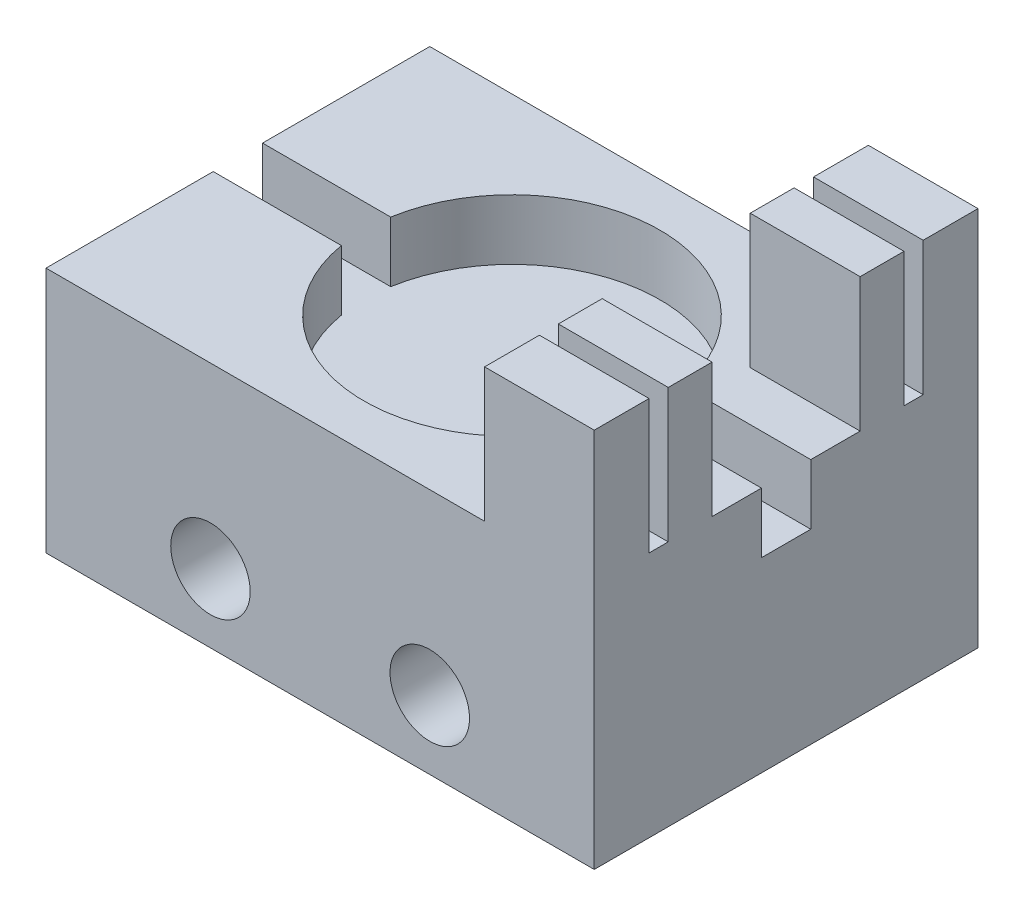
SolidWorks part; units mm, degrees
ref_plane "Front Plane" through (0, 0, 0) normal (0, 0, 1) x (1, 0, 0)
ref_plane "Top Plane" through (0, 0, 0) normal (0, 1, 0) x (1, 0, 0)
ref_plane "Right Plane" through (0, 0, 0) normal (1, 0, 0) x (0, 0, -1)
sketch "Sketch1" plane through (0, 0, 0) normal (0, 0, 1) x (1, 0, 0)
  line L1 (-25, -11.25) -> (25, -11.25)
  line L2 (-25, -11.25) -> (-25, 11.25)
  line L3 (-25, 11.25) -> (25, 11.25)
  line L4 (25, -11.25) -> (25, 11.25)
  line L5 (-25, -11.25) -> (25, 11.25) construction
  line L6 (-25, 11.25) -> (25, -11.25) construction
  point P0 (0, 0)
  dimension "D1" = 50
  dimension "D2" = 22.5
extrude "Boss-Extrude1" add sketch "Sketch1" along normal blind 35
sketch "Sketch2" plane through (0, 0, 35) normal (0, 0, 1) x (1, 0, 0)
  line L0 (25, 0) -> (-25, 0) construction
  line L1 (25, -11.25) -> (25, 11.25) construction
  line L2 (-25, 11.25) -> (-25, -11.25) construction
  line L3 (0, 11.25) -> (0, -11.25) construction
  line L4 (25, 11.25) -> (-25, 11.25) construction
  line L5 (-25, -11.25) -> (25, -11.25) construction
  circle A0 centre (10, -5) radius 3.625
  circle A1 centre (-10, -5) radius 3.625
  point P14 (0, 0)
  dimension "D2" = 7.25
  dimension "D1" = 10
  dimension "D3" = 6.25
extrude "Cut-Extrude1" cut sketch "Sketch2" against normal blind 35
sketch "Sketch3" plane through (0, 11.25, 0) normal (0, 1, 0) x (1, 0, 0)
  line L0 (25, 0) -> (3.2143, -15.25) construction
  line L1 (-25, -35) -> (25, -35) construction
  line L2 (25, -35) -> (0, -17.5) construction
  line L3 (-25, -35) -> (-25, 0) construction
  line L4 (25, -19.75) -> (13.3112, -19.75)
  line L5 (25, -19.75) -> (25, -15.25)
  line L6 (25, -15.25) -> (13.3112, -15.25)
  line L7 (-25, -19.75) -> (-25, -15.25)
  line L8 (-13.3112, -15.25) -> (-25, -15.25)
  line L9 (-13.3112, -19.75) -> (-25, -19.75)
  line L11 (-3.2143, -15.25) -> (-25, 0) construction
  line L12 (0, -17.5) -> (-25, -35) construction
  arc A0 (-13.3112, -19.75) -> (13.3112, -19.75) centre (0, -17.5) ccw
  arc A1 (13.3112, -15.25) -> (-13.3112, -15.25) centre (0, -17.5) ccw
  dimension "D1" = 27
  dimension "D2" = 4.5
extrude "Cut-Extrude2" cut sketch "Sketch3" against normal blind 5.5
sketch "Sketch4" plane through (0, 11.25, 0) normal (0, 1, 0) x (1, 0, 0)
  line L0 (25, -15.25) -> (25, 0) construction
  line L1 (25, 0) -> (15, 0)
  line L2 (25, 0) -> (25, -5)
  line L3 (25, -5) -> (15, -5)
  line L4 (15, 0) -> (15, -5)
  line L5 (25, -6.75) -> (14.976, -6.75)
  line L6 (25, -6.75) -> (25, -10.75)
  line L7 (25, -10.75) -> (14.976, -10.75)
  line L8 (14.976, -6.75) -> (14.976, -10.75)
  line L9 (25, -17.5) -> (-25, -17.5) construction
  line L10 (25, -19.75) -> (25, -15.25) construction
  line L11 (-25, -15.25) -> (-25, -19.75) construction
  line L12 (25, -24.25) -> (14.976, -24.25)
  line L13 (14.976, -28.25) -> (14.976, -24.25)
  line L14 (25, -28.25) -> (14.976, -28.25)
  line L15 (25, -28.25) -> (25, -24.25)
  line L16 (25, -30) -> (15, -30)
  line L17 (15, -35) -> (15, -30)
  line L18 (25, -35) -> (15, -35)
  line L19 (25, -35) -> (25, -30)
  dimension "D1" = 10
  dimension "D2" = 1.75
  dimension "D3" = 4
  dimension "D4" = 5
extrude "Boss-Extrude2" add sketch "Sketch4" along normal blind 12.2
